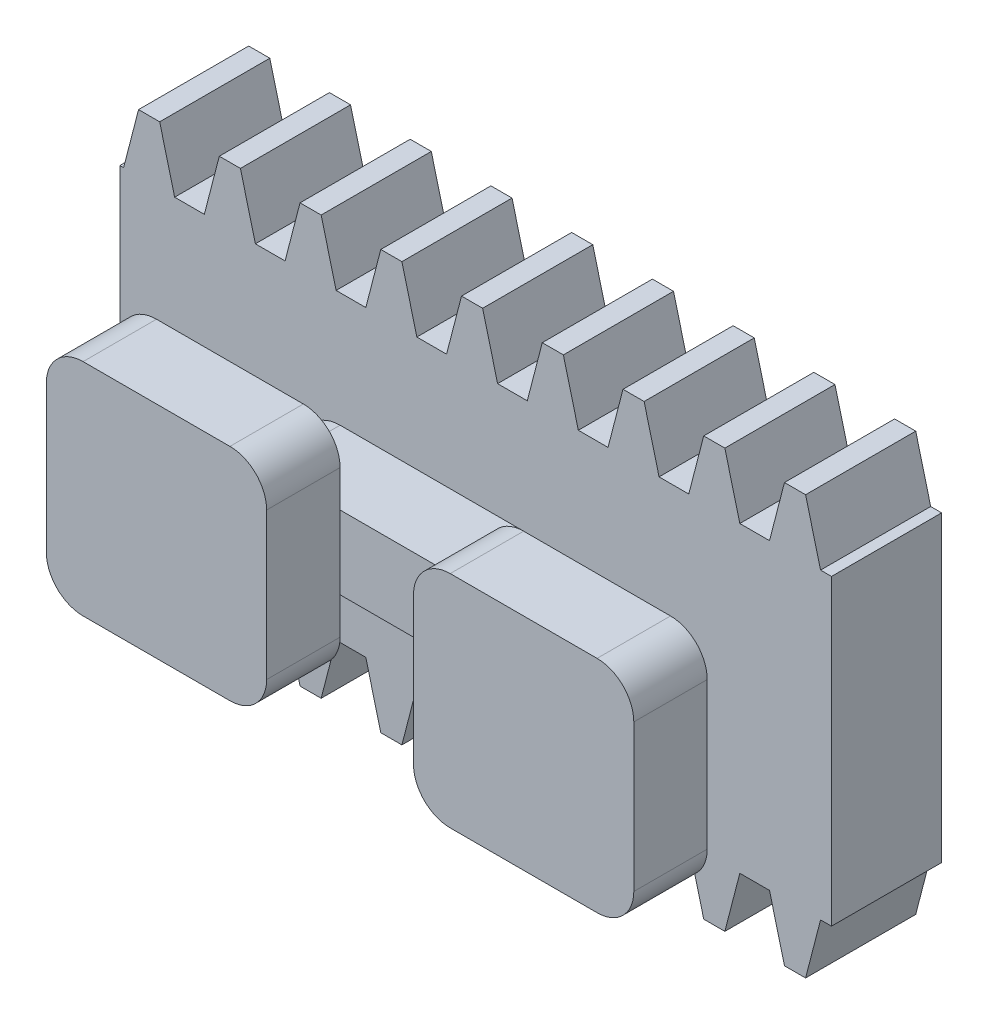
SolidWorks part; units mm, degrees
extrude "Blank" add sketch "BlankSke" against normal blind 3
sketch "BlankSke" plane through (0, 0, 0) normal (0, 0, 1) x (1, 0, 0)
  line L1 (0, 0) -> (25, 0)
  line L2 (0, 0) -> (0, 5.7)
  line L3 (0, 5.7) -> (25, 5.7)
  line L4 (25, 0) -> (25, 5.7)
  dimension "Length" = 25
ref_plane "Plane1" through (0, 0, 0) normal (0, 0, 1) x (1, 0, 0)
ref_plane "Plane2" through (0, 0, 0) normal (0, 1, 0) x (1, 0, 0)
ref_plane "Plane3" through (0, 0, 0) normal (1, 0, 0) x (0, 0, -1)
other "Configuration Table"
sketch "HoldingSke" plane through (0, 0, 0) normal (0, 1, 0) x (1, 0, 0)
  line L0 (0, 0) -> (0.1988, 1.4147)
  line L1 (-15, 0) -> (100, 0) construction
  line L2 (0, 0) -> (-2.1039, 2.3779)
  line L3 (0, 0) -> (-11.863, 4.5341)
  line L4 (0, 0) -> (8.4147, 1.9427)
  line L5 (0, 0) -> (-23.7986, -8.8762)
  line L6 (0, 0) -> (-10.5278, -7.1032)
  line L9 (-67.7845, 28.3722) -> (-43.5808, 34.6317)
  line L10 (-76.2, 3.0779) -> (-71.2, 3.0779)
  line L11 (0, 0) -> (-3, 0)
  line L12 (-76.2, 101.6) -> (-76.173, 101.6)
  line L13 (24.9733, 27.94) -> (52.9518, 28.4284)
  line L14 (24.9733, 27.94) -> (24.9743, 27.94)
  line L15 (24.9733, 27.94) -> (100.4006, 29.5858)
  circle A0 centre (0, 0) radius 19.05
  circle A1 centre (0, 0) radius 2.5
  circle A2 centre (0, 0) radius 12.7
  dimension "Num_teeth" = 13
  dimension "Width" = 3
  dimension "Length" = 25
  dimension "Pitch_height" = 5
sketch "TooCutSkeIll" plane through (0, 0, 0) normal (0, 0, 1) x (1, 0, 0)
  line L0 (-0.8064, 5.679) -> (-0.4386, 4.2569)
  line L1 (-0.2682, 4.125) -> (0.2682, 4.125)
  line L2 (0.4386, 4.2569) -> (0.8064, 5.679)
  line L3 (25, 5.7) -> (0, 5.7) construction
  line L4 (0, 0) -> (0, 64.897) construction
  line L5 (-13.208, 5) -> (12.954, 5) construction
  line L6 (0, 0) -> (25, 0) construction
  line L7 (0.6308, 5) -> (0.6308, 48.7463) construction
  line L8 (-0.6308, 5) -> (-0.6308, 48.7463) construction
  line L9 (0.8335, 5.7) -> (0.8335, 5.7254)
  line L10 (-0.8335, 5.7) -> (-0.8335, 5.7254)
  line L11 (-0.8335, 5.7254) -> (0.8335, 5.7254)
  arc A0 (0.2682, 4.125) -> (0.4386, 4.2569) centre (0.2682, 4.301) ccw
  arc A1 (-0.4386, 4.2569) -> (-0.2682, 4.125) centre (-0.2682, 4.301) ccw
  arc A2 (0.8335, 5.7) -> (0.8064, 5.679) centre (0.8335, 5.672) ccw
  arc A3 (-0.8064, 5.679) -> (-0.8335, 5.7) centre (-0.8335, 5.672) ccw
  dimension "Addendum_plus" = 0.7254
  dimension "Pitch_height" = 5
  dimension "Pressure_angle" = 14.5
  dimension "Gap_width" = 1.2616
  dimension "Dedendum" = 0.875
extrude "ToothCutIll" [suppressed] cut sketch "TooCutSkeIll" against normal through all
sketch "TooCutSkeSim" plane through (0, 0, 0) normal (0, 0, 1) x (1, 0, 0)
  line L0 (0.4045, 4.125) -> (-0.4045, 4.125)
  line L1 (0.8184, 5.7254) -> (0.4045, 4.125)
  line L2 (0, 17.4625) -> (0, 53.467) construction
  line L3 (0.8184, 5.7254) -> (-0.8184, 5.7254)
  line L6 (-0.8184, 5.7254) -> (-0.4045, 4.125)
  line L9 (-0.6308, 5) -> (0.6308, 5) construction
  line L10 (0, 0) -> (25, 0) construction
  line L11 (0.6308, 5) -> (0.6308, 53.467) construction
  line L12 (-0.6308, 5) -> (-0.6308, 53.467) construction
  dimension "Addendum_plus" = 0.7254
  dimension "Pitch_height" = 5
  dimension "Pressure_angle" = 14.5
  dimension "Gap_width" = 1.2616
  dimension "Dedendum" = 0.875
extrude "ToothCutSim" cut sketch "TooCutSkeSim" against normal through all
pattern_linear "TeethCuts" count 13 spacing 2.1991 along (1, 0, 0) of "ToothCutIll", "ToothCutSim"
mirror "镜向1" [suppressed]
mirror "镜向2" about plane through (0, 0, -3) normal (0, -1, 0) of "Blank", "ToothCutSim", "TeethCuts"
sketch "草图1" plane through (0, 0, 0) normal (-1, 0, 0) x (0, 0, 1)
  line L1 (0, 4.125) -> (0, -4.125) construction
  line L4 (-3, 0) -> (0, 0) construction
  line L5 (-3, 4.125) -> (-3, -4.125) construction
  line L7 (0, -3) -> (0, 3)
  line L8 (0, 3) -> (-2, 3.5)
  line L9 (-2, 3.5) -> (-2, -3.5)
  line L10 (0, -3) -> (-2, -3.5)
  point P11 (-2.5, 0)
  point P12 (-2, 0)
  dimension "D1" = 3
  dimension "D2" = 3.5
  dimension "D3" = 2
sketch "草图2" plane through (0, 0, -3) normal (0, 0, -1) x (-1, 0, 0)
  line L0 (0, 0) -> (-25, 0) construction
  line L1 (0, 4.125) -> (0, -4.125) construction
  line L2 (-25, -5.692) -> (-25, 5.692) construction
  circle A0 centre (-12.5, 0) radius 1.5
  dimension "D1" = 3
extrude "凸台-拉伸1" add sketch "草图2" along normal blind 2.5
sketch "草图3" plane through (0, 0, -5.5) normal (0, 0, -1) x (-1, 0, 0)
  circle A0 centre (-12.5, 0) radius 0.5
  dimension "D1" = 1
extrude "切除-拉伸3" cut sketch "草图3" against normal through all
sketch "草图4" plane through (0, 0, -3) normal (0, 0, -1) x (-1, 0, 0)
  line L0 (-12.5, 0) -> (-21.8848, 0) construction
  line L1 (-12.5, 0) -> (-2.5, 0) construction
  line L2 (-21.8848, 2.1496) -> (-21.8848, -2.1496)
  line L3 (-22.3956, 4.125) -> (-22.803, 5.7) construction
  line L4 (-2.5, 4.125) -> (-2.5, -4.125)
  line L6 (-1.7946, -4.125) -> (-2.6036, -4.125) construction
  line L7 (-22.3956, -4.125) -> (-22.803, -5.7) construction
  line L9 (-1.7946, 4.125) -> (-2.6036, 4.125) construction
  line L10 (-21.8848, 2.1496) -> (-21.8848, 5.9598)
  line L11 (-21.8848, 5.9598) -> (-25.6774, 5.9598)
  line L12 (-25.6774, 5.9598) -> (-25.6774, -6.5792)
  line L13 (-25.6774, -6.5792) -> (-21.8848, -6.5792)
  line L14 (-21.8848, -6.5792) -> (-21.8848, -2.1496)
  line L15 (-2.5, 4.125) -> (-2.5, 6.4022)
  line L16 (-2.5, 6.4022) -> (0, 6.4022)
  line L17 (0, 6.4022) -> (0, -6.0736)
  line L18 (0, -6.0736) -> (-2.5, -6.0736)
  line L19 (-2.5, -6.0736) -> (-2.5, -4.125)
  dimension "D2" = 10
extrude "切除-拉伸4" cut sketch "草图4" against normal blind 10
sketch "草图5" plane through (0, 0, 0) normal (0, 0, 1) x (1, 0, 0)
  line L0 (2.5, 2) -> (21.8848, 2)
  line L1 (2.5, 4.125) -> (2.5, -4.125) construction
  line L2 (21.8848, -4.125) -> (21.8848, 4.125) construction
  line L3 (21.8848, 2) -> (21.8848, -2)
  line L4 (21.8848, -2) -> (2.5, -2)
  line L5 (2.5, -2) -> (2.5, 2)
  point P8 (2.5, 0)
  point P9 (21.8848, 0)
  dimension "D1" = 4
sketch "草图6" plane through (0, 0, 0) normal (0, 0, 1) x (1, 0, 0)
  line L0 (1.1742, 0) -> (24.2349, 0) construction
  line L1 (7.5, 1) -> (7.5, -1)
  line L2 (7.5, -1) -> (17.5, -1)
  line L3 (17.5, -1) -> (17.5, 1)
  line L4 (17.5, 1) -> (7.5, 1)
  point P2 (17.5, 0)
  point P4 (12.5, 0)
  point P5 (7.5, 0)
  dimension "D1" = 2
  dimension "D2" = 10
  dimension "D3" = 5
extrude "凸台-拉伸3" add sketch "草图6" along normal blind 2
sketch "草图7" plane through (0, 0, 2) normal (0, 0, 1) x (1, 0, 0)
  line L0 (4.5, 3) -> (10.5, 3)
  line L1 (20.5, 3) -> (20.5, -3)
  line L2 (20.5, -3) -> (14.5, -3)
  line L3 (4.5, -3) -> (4.5, 3)
  line L5 (17.5, 1) -> (7.5, 1) construction
  line L6 (7.5, -1) -> (17.5, -1) construction
  line L7 (7.5, 1) -> (7.5, -1) construction
  line L8 (17.5, -1) -> (17.5, 1) construction
  line L9 (10.5, 3) -> (10.5, -3)
  line L10 (14.5, 3) -> (14.5, -3)
  line L11 (14.5, 3) -> (20.5, 3)
  line L12 (10.5, -3) -> (4.5, -3)
  dimension "D1" = 2
  dimension "D2" = 2
  dimension "D3" = 3
  dimension "D4" = 3
  dimension "D5" = 6
  dimension "D6" = 6
extrude "凸台-拉伸4" add sketch "草图7" along normal blind 2
fillet "圆角1" radius 1 4 edges at (17.5, -1, 1) (7.5, -1, 1) (17.5, 1, 1) (7.5, 1, 1)
fillet "圆角2" radius 1 8 edges at (4.5, -3, 3) (4.5, 3, 3) (10.5, 3, 3) (10.5, -3, 3) (14.5, -3, 3) (14.5, 3, 3) (20.5, 3, 3) (20.5, -3, 3)
equation "' \"Module@HoldingSke\" = 6.35"
equation "' \"Num_teeth@HoldingSke\" = 12"
equation "' \"Ap@HoldingSke\" =  20"
equation "' \"Ap@HoldingSke\" = 20"
equation "' \"Width@HoldingSke\" = 0.25 * 25.4"
equation "' \"Show_teeth@HoldingSke\" = 500"
equation "' \"Backlash@HoldingSke\" = 0.009 * 25.4"
equation "' \"Addendum_fac@HoldingSke\" = 1.0"
equation "' \"Dedendum_fac@HoldingSke\" = 1.25"
equation "' \"Dedendum_add@HoldingSke\" = 0.00005 * 25.4"
equation "' \"Clearance_fac@HoldingSke\" = 0.25"
equation "' \"Pitch_height@HoldingSke\" = 1 * 25.4"
equation "' \"Length@HoldingSke\" = 4.71 * 25.4"
equation "\"Pitch@HoldingSke\" = 1 / \"Module@HoldingSke\""
equation "\"MPH@HoldingSke\" = \"Dedendum_fac@HoldingSke\" / \"Pitch@HoldingSke\" + 2 * \"Dedendum_add@HoldingSke\" + 0.002 * 25.4"
equation "\"MPH@HoldingSke\" = ((sgn( \"MPH@HoldingSke\" - \"Pitch_height@HoldingSke\")+1)*( \"MPH@HoldingSke\" - \"Pitch_height@HoldingSke\"))/2 + \"Pitch_height@HoldingSke\""
equation "\"Blank_height@BlankSke\" = \"Pitch_height@HoldingSke\" + \"Addendum_fac@HoldingSke\"  / \"Pitch@HoldingSke\" "
equation "\"Length@BlankSke\" =  \"Length@HoldingSke\""
equation "\"Face_width@Blank\" = \"Width@HoldingSke\""
equation "\"Pressure_angle@TooCutSkeIll\" = \"Ap@HoldingSke\""
equation "\"Addendum_plus@TooCutSkeIll\" =  \"Addendum_fac@HoldingSke\"  / \"Pitch@HoldingSke\" + 0.001 *25.4"
equation "\"Dedendum@TooCutSkeIll\" = \"Dedendum_fac@HoldingSke\"  / \"Pitch@HoldingSke\""
equation "\"Pitch_height@TooCutSkeIll\" =  \"MPH@HoldingSke\""
equation "\"Gap_width@TooCutSkeIll\" = 3.14159265 / 2 / \"Pitch@HoldingSke\" + 6 * \"Backlash@HoldingSke\""
equation "\"Pressure_angle@TooCutSkeSim\" = \"Ap@HoldingSke\""
equation "\"Addendum_plus@TooCutSkeSim\" =  \"Addendum_fac@HoldingSke\"  / \"Pitch@HoldingSke\" + 0.001 * 25.4"
equation "\"Dedendum@TooCutSkeSim\" = \"Dedendum_fac@HoldingSke\"  / \"Pitch@HoldingSke\""
equation "\"Pitch_height@TooCutSkeSim\" =  \"MPH@HoldingSke\""
equation "\"Gap_width@TooCutSkeSim\" = 3.14159265 / 2 / \"Pitch@HoldingSke\" + 6 * \"Backlash@HoldingSke\""
equation "\"Root_fillet@TooCutSkeIll\" = \"Clearance_fac@HoldingSke\" / \"Pitch@HoldingSke\" + \"Dedendum_add@HoldingSke\""
equation "\"Break_rad@TooCutSkeIll\" = 0.02 / \"Pitch@HoldingSke\" * 2"
equation "\"Linear_pitch@TeethCuts\" = 3.14159265 / \"Pitch@HoldingSke\""
equation "\"Num_teeth@HoldingSke\" = int( ( \"Length@HoldingSke\" + 0 ) / (3.14159265 / \"Pitch@HoldingSke\")) + 0.9999  + 1"
equation " \"Num_teeth@TeethCuts\" = int( \"Show_teeth@HoldingSke\" ) + 1"
equation " \"Num_teeth@TeethCuts\" = ((sgn( \"Num_teeth@TeethCuts\" - \"Num_teeth@HoldingSke\" )-1)*( \"Num_teeth@TeethCuts\" - \"Num_teeth@HoldingSke\" ))/-2+ \"Num_teeth@HoldingSke\""
equation " \"Num_teeth@TeethCuts\" = ((sgn( \"Num_teeth@TeethCuts\" - 2.0)+1)*( \"Num_teeth@TeethCuts\" - 2.0))/2 +2.0"
